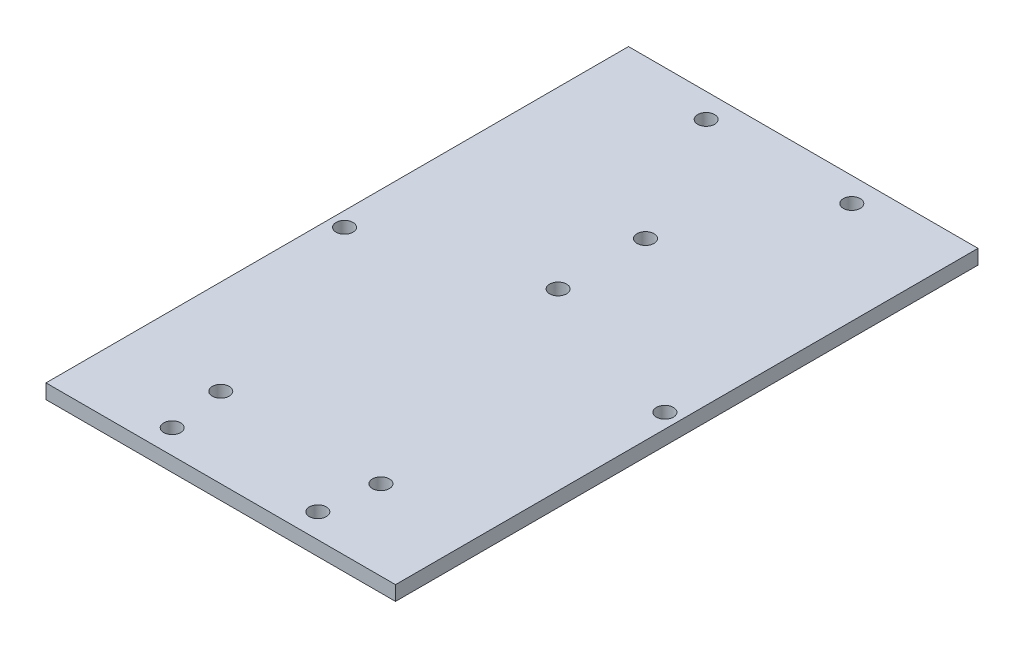
SolidWorks part; units mm, degrees
ref_plane "Front Plane" through (0, 0, 0) normal (0, 0, 1) x (1, 0, 0)
ref_plane "Top Plane" through (0, 0, 0) normal (0, 1, 0) x (1, 0, 0)
ref_plane "Right Plane" through (0, 0, 0) normal (1, 0, 0) x (0, 0, -1)
sketch "Sketch1" plane through (0, 0, 0) normal (0, 1, 0) x (1, 0, 0)
  line L0 (0, 0) -> (0, 50000) construction
  line L1 (36, -60) -> (-36, -60)
  line L2 (36, -60) -> (36, 60)
  line L3 (36, 60) -> (-36, 60)
  line L4 (-36, -60) -> (-36, 60)
  line L5 (36, -60) -> (-36, 60) construction
  line L6 (36, 60) -> (-36, -60) construction
  line L8 (0, 9.5) -> (0, -1.5)
  line L9 (0, 0) -> (50000, 0) construction
  circle A0 centre (-33, -1.5) radius 1.75
  circle A1 centre (33, -1.5) radius 1.75
  circle A2 centre (-16.5, -43.5) radius 1.75
  circle A3 centre (16.5, -43.5) radius 1.75
  circle A4 centre (0, 27.5) radius 1.75
  circle A5 centre (0, 9.5) radius 1.75
  circle A6 centre (-15, -55) radius 1.75
  circle A7 centre (15, -55) radius 1.75
  circle A8 centre (15, 55) radius 1.75
  circle A9 centre (-15, 55) radius 1.75
  point P0 (0, 0)
  point P19 (0, 0)
  point P27 (-16.75, -55)
  point P29 (36, 0)
  point P34 (0, 0)
  point P35 (0, 0)
  point P36 (0, 0)
  dimension "D3" = 3.5
  dimension "D4" = 3.5
  dimension "D5" = 33
  dimension "D6" = 3.5
  dimension "D7" = 3.5
  dimension "D10" = 3.5
  dimension "D11" = 3.5
  dimension "D15" = 3.5
  dimension "D16" = 3.5
  dimension "D17" = 15
  dimension "D19" = 66
  dimension "D1" = 120
  dimension "D2" = 72
  dimension "D8" = 42
  dimension "D9" = 16.5
  dimension "D13" = 18
  dimension "D14" = 11
  dimension "D18" = 5
extrude "Boss-Extrude1" add sketch "Sketch1" along normal blind 3 contours L4 L1 L2 L3 A7 A6 A5 A4 A3 A2 A1 A0 region at (0, 0, 58.6006)
